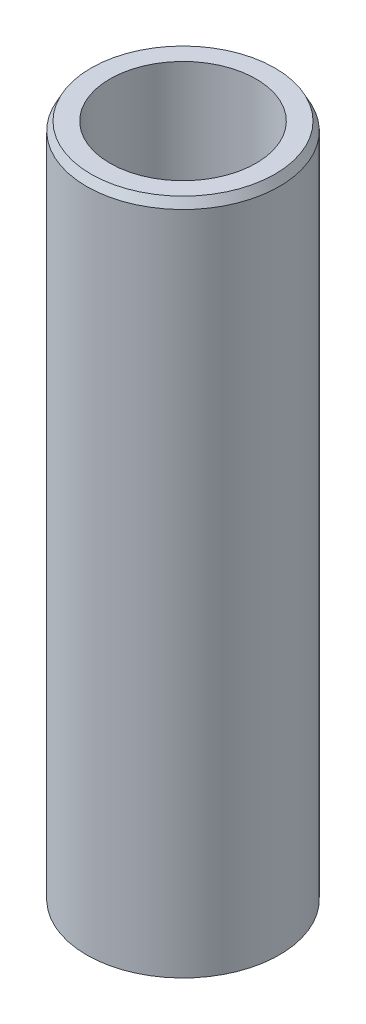
SolidWorks part; units mm, degrees
ref_plane "Front Plane" through (0, 0, 0) normal (0, 0, 1) x (1, 0, 0)
ref_plane "Top Plane" through (0, 0, 0) normal (0, 1, 0) x (1, 0, 0)
ref_plane "Right Plane" through (0, 0, 0) normal (1, 0, 0) x (0, 0, -1)
sketch "Sketch1" plane through (0, 0, 0) normal (0, 1, 0) x (1, 0, 0)
  circle A0 centre (0, 0) radius 47.5
  dimension "SHAFT_OD" = 95
extrude "Boss-Extrude1" add sketch "Sketch1" along normal blind 334.3008
sketch "Sketch2" plane through (0, 0, 0) normal (0, 1, 0) x (1, 0, 0)
  circle A0 centre (0, 0) radius 36.0101
  dimension "BORE_D" = 72.0201
extrude "Cut-Extrude1" cut sketch "Sketch2" along normal through all
chamfer "Chamfer1" distance 4.1627 angle 27.707 2 edges at (0, 334.3008, 47.5) (0, 0, 47.5) first distance on face at (0, 334.3008, 47.5) first distance on face at (0, 0, 36.0101)
